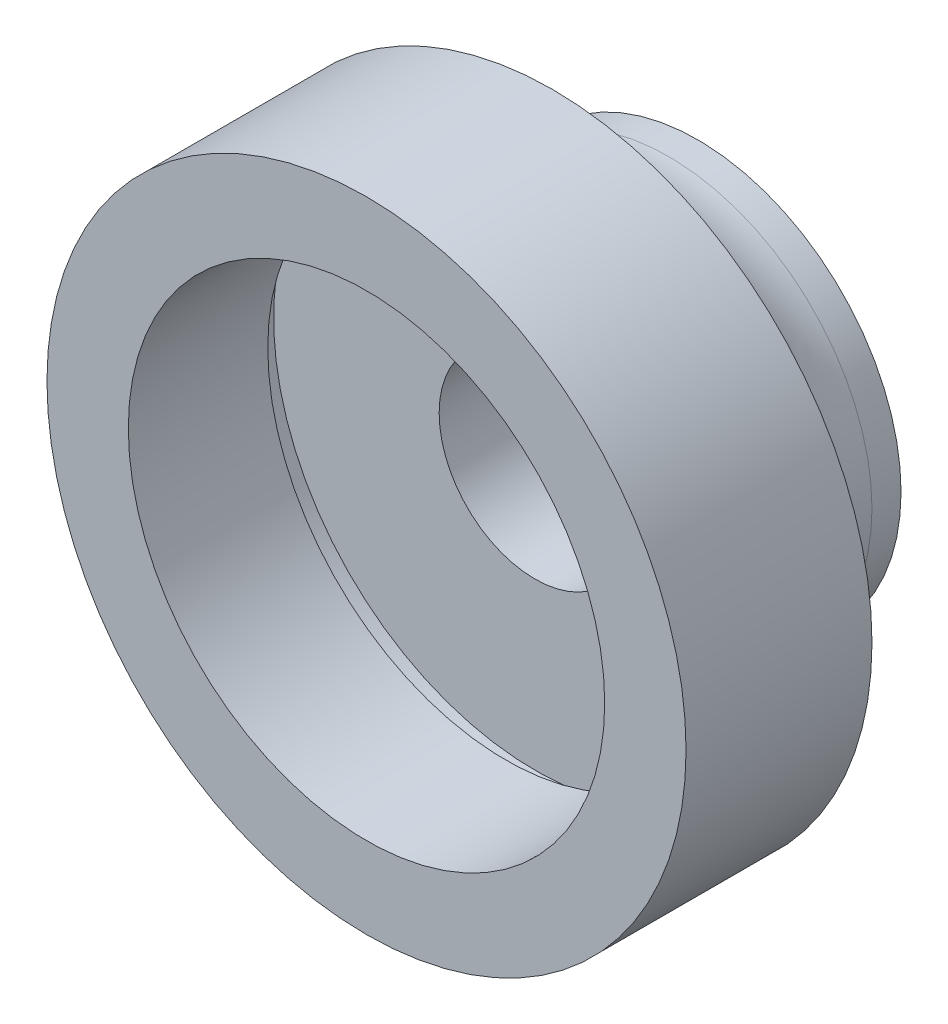
SolidWorks part; units mm, degrees
ref_plane "Front Plane" through (0, 0, 0) normal (0, 0, 1) x (1, 0, 0)
ref_plane "Top Plane" through (0, 0, 0) normal (0, 1, 0) x (1, 0, 0)
ref_plane "Right Plane" through (0, 0, 0) normal (1, 0, 0) x (0, 0, -1)
sketch "Sketch1" plane through (0, 0, 0) normal (0, 0, 1) x (1, 0, 0)
  circle A0 centre (0, 0) radius 1.625
  circle A1 centre (0, 0) radius 3.5
  dimension "D1" = 3.25
  dimension "D2" = 7
extrude "Boss-Extrude1" add sketch "Sketch1" along normal blind 1 and the other way blind 1.5
sketch "Sketch2" plane through (0, 0, 1) normal (0, 0, 1) x (1, 0, 0)
  circle A0 centre (0, 0) radius 5.5
  dimension "D1" = 11
extrude "Boss-Extrude2" add sketch "Sketch2" along normal blind 3.2
sketch "Sketch3" plane through (0, 0, 4.2) normal (0, 0, 1) x (1, 0, 0)
  circle A0 centre (0, 0) radius 4.1
  dimension "D1" = 8.2
extrude "Cut-Extrude1" cut sketch "Sketch3" against normal blind 2.9
sketch "Sketch4" plane through (0, 0, -1.5) normal (0, 0, -1) x (-1, 0, 0)
  circle A0 centre (0, 0) radius 1.65
extrude "Cut-Extrude2" cut sketch "Sketch4" against normal blind 10
fillet "Fillet2" radius 2 1 edges at (3.5, 0, 1)
sketch "Sketch5" plane through (0, 0, 1.3) normal (0, 0, 1) x (1, 0, 0)
  circle A0 centre (0, 0) radius 4.5
  dimension "D1" = 9
extrude "Cut-Extrude3" cut sketch "Sketch5" along normal blind 0.5
